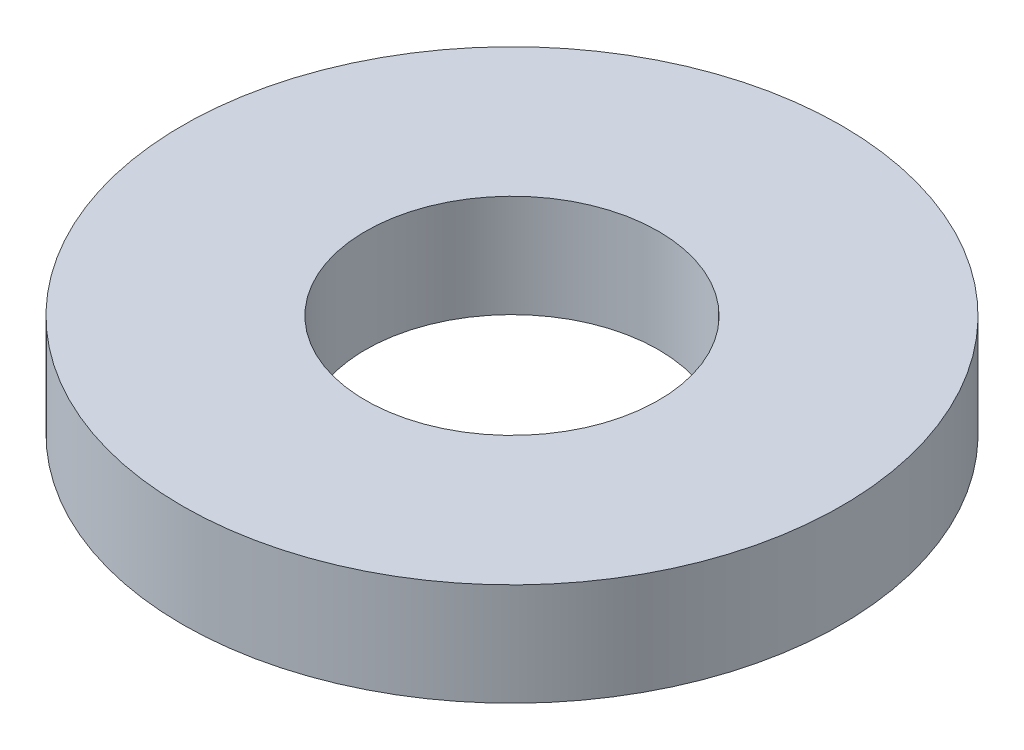
SolidWorks part; units mm, degrees
ref_plane "Front Plane" through (0, 0, 0) normal (0, 0, 1) x (1, 0, 0)
ref_plane "Top Plane" through (0, 0, 0) normal (0, 1, 0) x (1, 0, 0)
ref_plane "Right Plane" through (0, 0, 0) normal (1, 0, 0) x (0, 0, -1)
sketch "Sketch1" plane through (0, 0, 0) normal (0, 1, 0) x (1, 0, 0)
  circle A0 centre (0, 0) radius 67.5
  dimension "FLANGE_OD" = 135
extrude "Boss-Extrude1" add sketch "Sketch1" along normal blind 21
sketch "Sketch2" plane through (0, 0, 0) normal (0, 1, 0) x (1, 0, 0)
  circle A0 centre (0, 0) radius 30
  dimension "BORE_D" = 60
extrude "Cut-Extrude1" cut sketch "Sketch2" along normal through all
sketch "Sketch3" plane through (0, 21, 0) normal (0, 1, 0) x (1, 0, 0)
  circle A0 centre (0, 0) radius 24.3968 construction
  circle A1 centre (-24.3968, 0) radius 3.5344
  dimension "BOLT_D" = 7.0687
  dimension "BOLT_PCD" = 48.7937
extrude "Cut-Extrude2" cut sketch "Sketch3" against normal blind 16.6575 rebuild error yes
pattern_circular "CirPattern1" count 8 over 360 rebuild error yes
